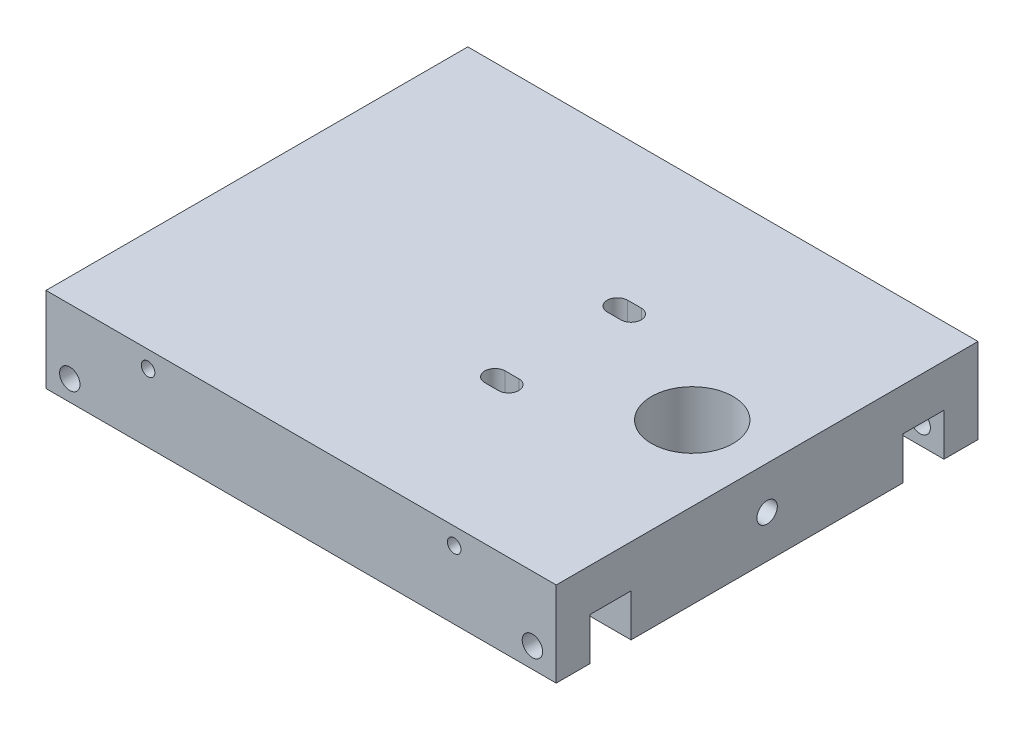
SolidWorks part; units mm, degrees
ref_plane "Front Plane" through (0, 0, 0) normal (0, 0, 1) x (1, 0, 0)
ref_plane "Top Plane" through (0, 0, 0) normal (0, 1, 0) x (1, 0, 0)
ref_plane "Right Plane" through (0, 0, 0) normal (1, 0, 0) x (0, 0, -1)
sketch "Sketch1" plane through (0, 0, 0) normal (0, 1, 0) x (1, 0, 0)
  line L0 (-75, 52) -> (75, 52)
  line L1 (-75, 62) -> (75, 62)
  line L2 (-75, 62) -> (-75, -62)
  line L3 (-75, -62) -> (75, -62)
  line L4 (75, 62) -> (75, -62)
  line L5 (0, -62) -> (0, 62) construction
  line L6 (-75, 0) -> (75, 0) construction
  line L7 (-75, 40) -> (75, 40)
  line L8 (-75, 40) -> (-75, -40)
  line L9 (-75, -40) -> (75, -40)
  line L10 (75, 40) -> (75, -40)
  line L11 (0, -40) -> (0, 40) construction
  line L12 (-75, 0) -> (75, 0) construction
  line L13 (-75, -52) -> (75, -52)
  circle A0 centre (53, 0) radius 12
  point P0 (0, 0)
  point P4 (0, 0)
  dimension "D7" = 24
  dimension "D1" = 124
  dimension "D2" = 150
  dimension "D3" = 80
  dimension "D4" = 150
  dimension "D5" = 12
  dimension "D6" = 12
  dimension "D8" = 22
  dimension "D9" = 150
extrude "Boss-Extrude1" add sketch "Sketch1" along normal blind 12.5 contours L2 L9 L4 L7 | L13 L2 L3 L4 | L4 L1 L2 L0 region at (0, 0, -57) region at (-2.0763, 0, 0) region at (0, 0, 57)
extrude "Boss-Extrude2" add sketch "Sketch1<3>" along normal blind 12.5 from surface contours L13 L2 L3 L4 | L2 L13 L4 L9 | L2 L7 L4 L0 | L4 L1 L2 L0 | L2 L9 L4 L7 region at (0, 0, -57) region at (0, 0, -46) region at (-2.0763, 0, 0) region at (0, 0, 46) region at (0, 0, 57) starting at face at (53, 12.5, 12)
sketch "Sketch1<3>" plane through (0, 0, 0) normal (0, 1, 0) x (1, 0, 0) same geometry as "Sketch1"
sketch "Sketch2" plane through (0, 0, 0) normal (0, -1, 0) x (1, 0, 0)
  line L0 (97.0851, 0) -> (-97.0851, 0) construction
  line L1 (13, 21) -> (17, 21)
  line L2 (13, 15) -> (17, 15)
  line L3 (-75, 62) -> (75, 62) construction
  line L4 (75, -40) -> (75, 40) construction
  line L5 (13, -15) -> (17, -15)
  line L6 (13, -21) -> (17, -21)
  line L7 (13, 25) -> (17, 25)
  line L8 (13, 11) -> (17, 11)
  line L9 (13, -11) -> (17, -11)
  line L10 (13, -25) -> (17, -25)
  circle A0 centre (13, 18) radius 3
  circle A1 centre (17, 18) radius 3
  circle A2 centre (17, -18) radius 3
  circle A3 centre (13, -18) radius 3
  arc A4 (17, 11) -> (17, 25) centre (17, 18) ccw
  arc A5 (13, 25) -> (13, 11) centre (13, 18) ccw
  arc A6 (17, -11) -> (17, -25) centre (17, -18) cw
  arc A7 (13, -25) -> (13, -11) centre (13, -18) cw
  point P4 (0, 0)
  dimension "D1" = 6
  dimension "D2" = 6
  dimension "D5" = 58
  dimension "D6" = 14
  dimension "D7" = 14
  dimension "D3" = 4
  dimension "D4" = 41
extrude "Cut-Extrude1" cut sketch "Sketch2" against normal through all contours A3 A2 | L5 A3 A2 | A3 A2 | A2 A3 L6 | A2 A3 | A1 A0 | A1 L1 A0 | A0 A1 | A1 A0 | A1 A0 L2 region at (12.4388, 0, 18) region at (15, 0, 20.7769) region at (17.5612, 0, 18) region at (15, 0, 15.2231) region at (15, 0, 18) region at (12.4388, 0, -18) region at (15, 0, -15.2231) region at (17.5612, 0, -18) region at (15, 0, -20.7769) region at (15, 0, -18)
extrude "Cut-Extrude2" cut sketch "Sketch2<3>" against normal blind 10 contours L7 A5 L8 A4 A1 L2 A0 L1 | A7 L10 A6 L9 L6 A3 L5 A2 region at (15, 0, 24.772) region at (15, 0, -11.228)
sketch "Sketch2<3>" plane through (0, 0, 0) normal (0, -1, 0) x (1, 0, 0) same geometry as "Sketch2"
sketch "Sketch3" plane through (75, 0, 0) normal (1, 0, 0) x (0, 0, -1)
  line L0 (40, 0) -> (-40, 0) construction
  circle A0 centre (0, 12.5) radius 3
  dimension "D1" = 6
  dimension "D2" = 12.5
extrude "Cut-Extrude3" cut sketch "Sketch3" against normal blind 15
sketch "Sketch4" plane through (0, 0, 62) normal (0, 0, 1) x (1, 0, 0)
  line L0 (75, 25) -> (-75, 25) construction
  line L1 (-45, 20) -> (45, 20) construction
  line L3 (-75, 0) -> (75, 0) construction
  line L4 (-75, 25) -> (-75, 0) construction
  line L5 (0, -55) -> (0, 55) construction
  circle A0 centre (-45, 20) radius 2
  circle A1 centre (45, 20) radius 2
  circle A2 centre (-68, 6) radius 3
  circle A3 centre (68, 6) radius 3
  point P6 (0, 20)
  dimension "D1" = 4
  dimension "D2" = 4
  dimension "D5" = 6
  dimension "D3" = 90
  dimension "D4" = 5
  dimension "D6" = 6
  dimension "D7" = 7
extrude "Cut-Extrude4" cut sketch "Sketch4" against normal blind 18
extrude "Cut-Extrude5" cut sketch "Sketch4<2>" along normal blind 18 from surface starting at face at (0, 12.5, -62)
sketch "Sketch4<2>" plane through (0, 0, 62) normal (0, 0, 1) x (1, 0, 0) same geometry as "Sketch4"
sketch "Sketch5" plane through (0, 25, 0) normal (0, 1, 0) x (1, 0, 0)
  line L0 (13, -15) -> (17, -15) construction
  line L1 (13, -21) -> (17, -21) construction
  line L2 (13, 21) -> (17, 21) construction
  line L3 (13, 15) -> (17, 15) construction
  line L4 (-75, 62) -> (-75, -62)
  line L5 (-75, -62) -> (75, -62)
  line L6 (75, -62) -> (75, 62)
  line L7 (75, 62) -> (-75, 62)
  line L8 (-75, 62) -> (-75, -62)
  line L9 (-75, -62) -> (75, -62)
  line L10 (75, -62) -> (75, 62)
  line L11 (75, 62) -> (-75, 62)
  line L12 (13, -15) -> (17, -15)
  line L13 (13, -21) -> (17, -21)
  line L14 (13, 21) -> (17, 21)
  line L15 (13, 15) -> (17, 15)
  circle A0 centre (53, 0) radius 12 construction
  arc A1 (13, -15) -> (13, -21) centre (13, -18) ccw construction
  arc A2 (17, -21) -> (17, -15) centre (17, -18) ccw construction
  arc A3 (13, 21) -> (13, 15) centre (13, 18) ccw construction
  arc A4 (17, 15) -> (17, 21) centre (17, 18) ccw construction
  circle A5 centre (53, 0) radius 12
  arc A6 (13, -15) -> (13, -21) centre (13, -18) ccw
  arc A7 (17, -21) -> (17, -15) centre (17, -18) ccw
  arc A8 (13, 21) -> (13, 15) centre (13, 18) ccw
  arc A9 (17, 15) -> (17, 21) centre (17, 18) ccw
  point P15 (13.6277, 17.5018)
  point P19 (87.6177, -5.5827)
  dimension "D2" = 40
  dimension "D3" = 36
  dimension "D4" = 18
  dimension "D5" = 22
  dimension "D1" = 0
